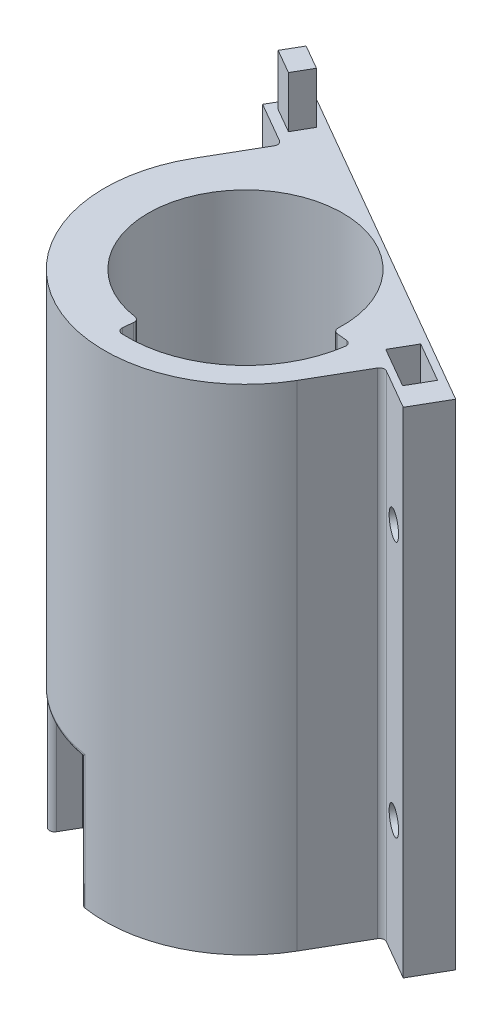
SolidWorks part; units mm, degrees
ref_plane "Front Plane" through (0, 0, 0) normal (0, 0, 1) x (1, 0, 0)
ref_plane "Top Plane" through (0, 0, 0) normal (0, 1, 0) x (1, 0, 0)
ref_plane "Right Plane" through (0, 0, 0) normal (1, 0, 0) x (0, 0, -1)
sketch "Sketch1" plane through (0, 0, 0) normal (0, 1, 0) x (1, 0, 0)
  line L0 (0, 19) -> (0, 15.5) construction
  line L1 (0, -15.5) -> (0, -19) construction
  line L2 (0, 15.5) -> (-13.4234, 7.75) construction
  line L3 (-9.5, 16.4545) -> (-7, 12.1244) construction
  line L4 (-9.5, 16.4545) -> (0, 0) construction
  line L5 (9.6092, 16.3909) -> (-9.6092, -16.3909) construction
  circle A0 centre (0, 0) radius 19
  circle A1 centre (0, 15.5) radius 1.5
  circle A2 centre (13.4234, 7.75) radius 1.5
  circle A3 centre (13.4234, -7.75) radius 1.5
  circle A4 centre (0, -15.5) radius 1.5
  circle A5 centre (-13.4234, -7.75) radius 1.5
  circle A6 centre (-13.4234, 7.75) radius 1.5
  circle A7 centre (-2.75, 4.7631) radius 8.5
  circle A8 centre (5.4995, -0.0732) radius 8.5
  point P6 (-6.7117, 11.625)
  dimension "D1" = 38
  dimension "D2" = 3
  dimension "D5" = 17
  dimension "D3" = 3.5
  dimension "D6" = 3.5
  dimension "D7" = 5
  dimension "D4" = 6
ref_plane "Plane1" through (0, 0, 0) normal (0, 1, 0) x (1, 0, 0)
sketch "Sketch2" plane through (0, 0, 0) normal (0, 1, 0) x (1, 0, 0)
  line L0 (9.5, 16.4545) -> (7.75, 13.4234) construction
  line L1 (0, 19) -> (0, 15.5) construction
  line L2 (9.5, 16.4545) -> (0, 0) construction
  line L3 (0, 15.5) -> (13.4234, 7.75) construction
  line L4 (-13.8157, 31.0705) -> (33.8157, 3.5705)
  line L5 (33.8157, 3.5705) -> (23.8157, -13.75)
  line L6 (23.8157, -13.75) -> (-23.8157, 13.75)
  line L7 (-23.8157, 13.75) -> (-13.8157, 31.0705)
  line L8 (33.8157, 3.5705) -> (42.476, -1.4295)
  line L9 (42.476, -1.4295) -> (38.726, -7.9247)
  line L10 (38.726, -7.9247) -> (30.0657, -2.9247)
  line L11 (30.0657, -2.9247) -> (33.8157, 3.5705)
  line L12 (-13.8157, 31.0705) -> (-22.476, 36.0705)
  line L13 (-22.476, 36.0705) -> (-26.226, 29.5753)
  line L14 (-26.226, 29.5753) -> (-17.5657, 24.5753)
  line L15 (-13.8157, 31.0705) -> (-17.5657, 24.5753)
  circle A0 centre (7.75, 13.4234) radius 1.5 construction
  arc A1 (-23.8157, 13.75) -> (23.8157, -13.75) centre (0, 0) ccw
  circle A2 centre (0, 15.5) radius 1.5 construction
  circle A3 centre (0, 0) radius 19 construction
  point P19 (6.7117, 11.625)
  dimension "D1" = 10
  dimension "D2" = 55
  dimension "D3" = 7.5
  dimension "D4" = 10
  dimension "D5" = 7.5
  dimension "D6" = 1
extrude "Boss-Extrude1" add sketch "Sketch2" along normal blind 96.5 contours L6 A1 | L7 L6 L5 L4 | L9 L10 L11 L8 | L14 L15 L12 L13 region at (5, 0, -8.6603) region at (-5.8357, 0, 10.1077)
extrude "Cut-Extrude4" cut sketch "Sketch1" along normal through all from offset 6.5 contours A0
extrude "Cut-Extrude5" cut sketch "Sketch1<5>" along normal blind 6.5 contours A7 A8 | A2 | A3 | A4 | A5 | A6 | A1 | A7 region at (-4.7233, 0, -5.92)
sketch "Sketch1<5>" plane through (0, 0, 0) normal (0, 1, 0) x (1, 0, 0) same geometry as "Sketch1"
sketch "Sketch5" plane through (6.25, 0, -10.8253) normal (-0.5, 0, 0.866) x (0.866, 0, 0.5)
  line L0 (-32.5, 96.5) -> (-32.5, 0) construction
  line L1 (-37.5, 96.5) -> (-27.5, 96.5) construction
  line L2 (-37.5, 0) -> (-27.5, 0) construction
  line L3 (-32.5, 73.25) -> (-32.5, 23.25) construction
  circle A0 centre (-32.5, 73.25) radius 2.5
  circle A1 centre (-32.5, 23.25) radius 2.5
  point P14 (-32.5, 48.25)
  dimension "D1" = 5
  dimension "D2" = 50
extrude "Cut-Extrude6" cut sketch "Sketch5" against normal through all both and the other way through all
ref_plane "Plane2" through (0, 0, 0) normal (-0.866, 0, -0.5) x (-0.5, 0, 0.866)
mirror "Mirror1" about plane through (0, 0, 0) normal (-0.866, 0, -0.5) of "Cut-Extrude6"
sketch "Sketch6" plane through (0, 96.5, 0) normal (0, 1, 0) x (1, 0, 0)
  line L0 (-13.75, -23.8157) -> (0, 0) construction
  line L1 (-8, -13.8564) -> (-18, -13.8564)
  line L2 (-18, -13.8564) -> (-23, -22.5167)
  line L3 (-23, -22.5167) -> (-18, -31.1769)
  line L4 (-18, -31.1769) -> (-8, -31.1769)
  line L5 (-8, -31.1769) -> (-3, -22.5167)
  line L6 (-3, -22.5167) -> (-8, -13.8564)
  line L7 (42.476, -1.4295) -> (38.726, -7.9247) construction
  circle A0 centre (-13, -22.5167) radius 8.6603 construction
  arc A1 (-23.8157, 13.75) -> (23.8157, -13.75) centre (0, 0) ccw construction
  dimension "D1" = 26
  dimension "D2" = 10
extrude "Cut-Extrude8" cut sketch "Sketch6" along normal blind 25 from surface starting at face at (0, 0, -14)
sketch "Sketch7" plane through (0, 96.5, 0) normal (0, 1, 0) x (1, 0, 0)
  line L0 (0, 0) -> (22.8919, -2.2268)
  line L1 (0, 0) -> (-2.2268, -22.8919)
  line L2 (30.0657, -2.9247) -> (22.8919, -2.2268) construction
  circle A0 centre (0, 0) radius 19
  arc A2 (-5.5, -18.1865) -> (-13, -13.8564) centre (0, 0) ccw construction
  circle A3 centre (0, 0) radius 23
  circle M8 centre (0, 0) radius 19
  dimension "D1" = 38
  dimension "D2" = 46
  dimension "D3" = 90
extrude "Cut-Extrude9" cut sketch "Sketch7" against normal up to surface (90 mm away) contours L1 A3 L0 M8 region at (20.8695, 96.5, 2.3601) up to face at (0, 6.5, -14)
sketch "Sketch8" plane through (0, 0, 0) normal (0.9953, 0, 0.0968) x (0.0968, 0, -0.9953)
  line L1 (-23, 6.5) -> (-17, 6.5)
  line L2 (-23, 6.5) -> (-23, 25)
  line L3 (-23, 25) -> (-17, 25)
  line L4 (-17, 6.5) -> (-17, 25)
  line L5 (-23, 6.5) -> (-17, 25) construction
  line L6 (-23, 25) -> (-17, 6.5) construction
  point P0 (-20, 15.75)
  dimension "D1" = 18.5
  dimension "D2" = 6
extrude "Cut-Extrude10" cut sketch "Sketch8" against normal blind 10
fillet "Fillet3" radius 1 6 edges at (-17.5657, 48.25, -24.5753) (30.0657, 48.25, 2.9247) (-1.8396, 60.75, 18.9107) (-2.2268, 60.75, 22.8919) (18.9107, 51.5, 1.8396) (22.8919, 51.5, 2.2268)
fillet "Fillet6" radius 1 10 edges at (-1.8901, 25, 22.6235) (-2.0309, 25, 20.8776) (-2.1414, 25, 19.1685) (-5.5504, 12.5, 26.9341) (-13.75, 25, 23.8157) (-10.5, 6.5, 13.8564) (-5.5, 6.5, 18.1865) (-13, 15.75, 13.8564) (-8.2687, 25, 17.1064) (-20.5504, 12.5, 18.2738)
sketch "Sketch10" plane through (0, 96.5, 0) normal (0, 1, 0) x (1, 0, 0)
  line L4 (-19.0723, 27.4659) -> (-23.8354, 30.2159)
  line L5 (-23.8354, 30.2159) -> (-21.8354, 33.68)
  line L6 (-21.8354, 33.68) -> (-17.0723, 30.93)
  line L7 (-19.0723, 27.4659) -> (-17.0723, 30.93)
  line L8 (-22.476, 36.0705) -> (-26.226, 29.5753) construction
  line L9 (-22.476, 36.0705) -> (42.476, -1.4295) construction
  line L10 (-18.4317, 25.0753) -> (-14.6817, 31.5705) construction
  line L11 (-26.226, 29.5753) -> (-18.4317, 25.0753) construction
  point P2 (0, 0)
  point P3 (0, 0)
  point P6 (0, 0)
  dimension "D1" = 1.75
  dimension "D2" = 1.75
  dimension "D3" = 1.75
  dimension "D4" = 1.75
extrude "Boss-Extrude2" add sketch "Sketch10" along normal blind 10
sketch "Sketch11" plane through (0, 96.5, 0) normal (0, 1, 0) x (1, 0, 0)
  line L0 (29.7266, 4.488) -> (37.5208, -0.012)
  line L1 (37.5208, -0.012) -> (35.0208, -4.3422)
  line L2 (35.0208, -4.3422) -> (27.2266, 0.1578)
  line L3 (27.2266, 0.1578) -> (29.7266, 4.488)
  line L5 (42.476, -1.4295) -> (38.726, -7.9247) construction
  line L7 (38.1458, 1.0705) -> (34.3958, -5.4247) construction
  line L8 (-22.476, 36.0705) -> (42.476, -1.4295) construction
  line L9 (38.726, -7.9247) -> (30.9317, -3.4247) construction
  point P14 (36.2708, -2.1771)
  point P15 (36.2708, -2.1771)
  dimension "D1" = 5
  dimension "D2" = 9
  dimension "D3" = 5
extrude "Cut-Extrude11" cut sketch "Sketch11" against normal blind 10
